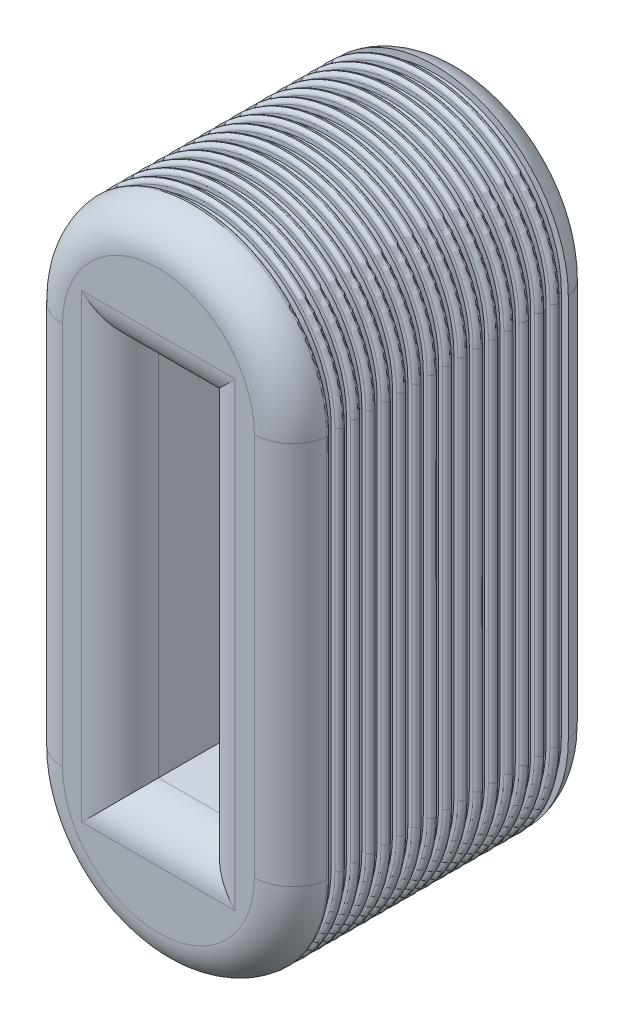
SolidWorks part; units mm, degrees
ref_plane "Front Plane" through (0, 0, 0) normal (0, 0, 1) x (1, 0, 0)
ref_plane "Top Plane" through (0, 0, 0) normal (0, 1, 0) x (1, 0, 0)
ref_plane "Right Plane" through (0, 0, 0) normal (1, 0, 0) x (0, 0, -1)
sketch "Sketch1" plane through (0, 0, 0) normal (0, 0, 1) x (1, 0, 0)
  line L0 (0, 2.5) -> (0, -2.5) construction
  line L1 (-0.5, 2.5) -> (0.5, 2.5)
  line L2 (-0.5, 2.5) -> (-0.5, -2.5)
  line L3 (-0.5, -2.5) -> (0.5, -2.5)
  line L4 (0.5, 2.5) -> (0.5, -2.5)
  line L5 (-0.5, 2.5) -> (0.5, -2.5) construction
  line L6 (-0.5, -2.5) -> (0.5, 2.5) construction
  line L7 (1.75, 2.5) -> (1.75, -2.5)
  line L8 (-1.75, 2.5) -> (-1.75, -2.5)
  arc A0 (1.75, 2.5) -> (-1.75, 2.5) centre (0, 2.5) ccw
  arc A1 (-1.75, -2.5) -> (1.75, -2.5) centre (0, -2.5) ccw
  point P0 (0, 0)
  point P8 (0, 0)
  dimension "D1" = 1
  dimension "D2" = 5
  dimension "D3" = 3.5
extrude "Winding profile" add sketch "Sketch1" along normal blind 4
fillet "Fillet1" radius 0.5 16 edges at (1.75, 0, 0) (0, -4.25, 0) (-1.75, 0, 0) (1.75, 0, 4) (0, -4.25, 4) (-1.75, 0, 4) (0, 4.25, 0) (0, 4.25, 4) (-0.5, 0, 4) (0, -2.5, 4) (0.5, 0, 4) (0, 2.5, 4) (0, -2.5, 0) (-0.5, 0, 0) (0, 2.5, 0) (0.5, 0, 0)
ref_plane "Plane1" through (0, 0, 3.5) normal (0, 0, -1) x (-1, 0, 0)
sketch "Sketch2" plane through (0, 0, 3.5) normal (0, 0, -1) x (-1, 0, 0)
  line L0 (1.75, -2.5) -> (1.75, 2.5) construction
  line L1 (1.75, -2.5) -> (1.75, 2.5)
  line L2 (-1.75, 2.5) -> (-1.75, -2.5) construction
  line L3 (-1.75, 2.5) -> (-1.75, -2.5)
  line L4 (-1.65, 2.5) -> (-1.65, -2.5)
  line L5 (1.65, -2.5) -> (1.65, 2.5)
  arc A0 (1.75, 2.5) -> (-1.75, 2.5) centre (0, 2.5) ccw construction
  arc A1 (1.75, 2.5) -> (-1.75, 2.5) centre (0, 2.5) ccw
  arc A2 (-1.75, -2.5) -> (1.75, -2.5) centre (0, -2.5) ccw construction
  arc A3 (-1.75, -2.5) -> (1.75, -2.5) centre (0, -2.5) ccw
  arc A4 (1.65, 2.5) -> (-1.65, 2.5) centre (0, 2.5) ccw
  arc A5 (-1.65, -2.5) -> (1.65, -2.5) centre (0, -2.5) ccw
  dimension "D1" = 0.1
extrude "Cut-Extrude1" cut sketch "Sketch2" along normal blind 0.1
pattern_linear "LPattern1" count 16 spacing 0.2 along (0, 0, -1) of "Cut-Extrude1"
fillet "Fillet3" radius 0.05 128 edges at (-1.65, 0, 0.5) (0, -4.15, 0.5) (1.65, 0, 0.5) (1.75, 0, 0.5) (0, -4.25, 0.5) (-1.75, 0, 0.5) (-1.75, 0, 0.6) (0, -4.25, 0.6) (1.75, 0, 0.6) (-1.75, 0, 0.7) (0, -4.25, 0.7) (1.75, 0, 0.7) (-1.75, 0, 0.8) (0, -4.25, 0.8) (1.75, 0, 0.8) (-1.75, 0, 0.9) (0, -4.25, 0.9) (1.75, 0, 0.9) (-1.75, 0, 1) (0, -4.25, 1) (1.75, 0, 1) (-1.75, 0, 1.1) (0, -4.25, 1.1) (1.75, 0, 1.1) (-1.75, 0, 1.2) (0, -4.25, 1.2) (1.75, 0, 1.2) (-1.75, 0, 1.3) (0, -4.25, 1.3) (1.75, 0, 1.3) (-1.75, 0, 1.4) (0, -4.25, 1.4) (1.75, 0, 1.4) (-1.75, 0, 1.5) (0, -4.25, 1.5) (1.75, 0, 1.5) (-1.75, 0, 1.6) (0, -4.25, 1.6) (1.75, 0, 1.6) (-1.75, 0, 1.7) (0, -4.25, 1.7) (1.75, 0, 1.7) (-1.75, 0, 1.8) (0, -4.25, 1.8) (1.75, 0, 1.8) (-1.75, 0, 1.9) (0, -4.25, 1.9) (1.75, 0, 1.9) (-1.75, 0, 2) (0, -4.25, 2) (1.75, 0, 2) (-1.75, 0, 2.1) (0, -4.25, 2.1) (1.75, 0, 2.1) (-1.75, 0, 2.2) (0, -4.25, 2.2) (1.75, 0, 2.2) (-1.75, 0, 2.3) (0, -4.25, 2.3) (1.75, 0, 2.3) (-1.75, 0, 2.4) (0, -4.25, 2.4) (1.75, 0, 2.4) (-1.75, 0, 2.5) (0, -4.25, 2.5) (1.75, 0, 2.5) (-1.75, 0, 2.6) (0, -4.25, 2.6) (1.75, 0, 2.6) (-1.75, 0, 2.7) (0, -4.25, 2.7) (1.75, 0, 2.7) (-1.75, 0, 2.8) (0, -4.25, 2.8) (1.75, 0, 2.8) (-1.75, 0, 2.9) (0, -4.25, 2.9) (1.75, 0, 2.9) (-1.75, 0, 3) (0, -4.25, 3) (1.75, 0, 3) (-1.75, 0, 3.1) (0, -4.25, 3.1) (1.75, 0, 3.1) (-1.75, 0, 3.2) (0, -4.25, 3.2) (1.75, 0, 3.2) (-1.75, 0, 3.3) (0, -4.25, 3.3) (1.75, 0, 3.3) (-1.75, 0, 3.4) (0, -4.25, 3.4) (1.75, 0, 3.4) (-1.75, 0, 3.5) (0, -4.25, 3.5) (1.75, 0, 3.5) (0, 4.15, 0.5) (0, 4.25, 0.5) (0, 4.25, 0.6) (0, 4.25, 0.7) (0, 4.25, 0.8) (0, 4.25, 0.9) (0, 4.25, 1) (0, 4.25, 1.1) (0, 4.25, 1.2) (0, 4.25, 1.3) (0, 4.25, 1.4) (0, 4.25, 1.5) (0, 4.25, 1.6) (0, 4.25, 1.7) (0, 4.25, 1.8) (0, 4.25, 1.9) (0, 4.25, 2) (0, 4.25, 2.1) (0, 4.25, 2.2) (0, 4.25, 2.3) (0, 4.25, 2.4) (0, 4.25, 2.5) (0, 4.25, 2.6) (0, 4.25, 2.7) (0, 4.25, 2.8) (0, 4.25, 2.9) (0, 4.25, 3) (0, 4.25, 3.1) (0, 4.25, 3.2) (0, 4.25, 3.3) (0, 4.25, 3.4) (0, 4.25, 3.5)
